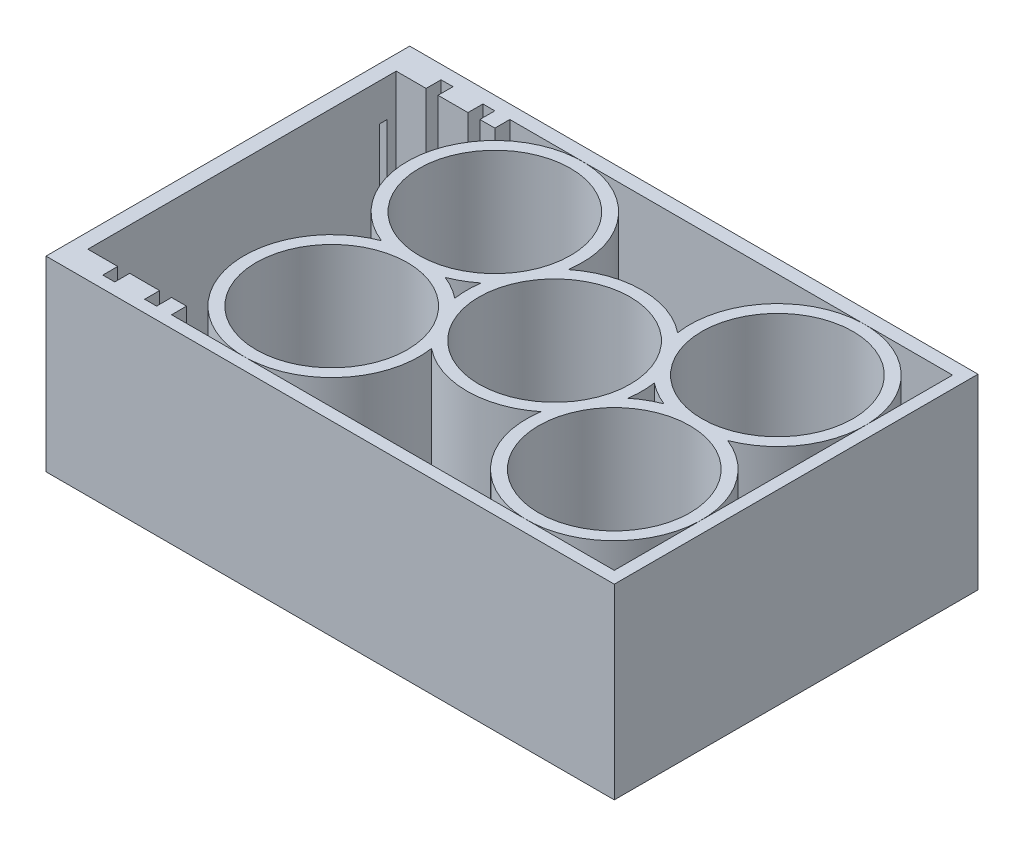
SolidWorks part; units mm, degrees
ref_plane "Front Plane" through (0, 0, 0) normal (0, 0, 1) x (1, 0, 0)
ref_plane "Top Plane" through (0, 0, 0) normal (0, 1, 0) x (1, 0, 0)
ref_plane "Right Plane" through (0, 0, 0) normal (1, 0, 0) x (0, 0, -1)
sketch "Sketch1" plane through (0, 0, 0) normal (0, 1, 0) x (1, 0, 0)
  line L0 (22.3334, 17.5114) -> (22.3334, 7.3964)
  line L1 (22.3334, 29.2264) -> (3.428, 18.3114)
  line L2 (3.428, 18.3114) -> (-15.4773, 29.2264)
  line L3 (-15.4773, 17.5114) -> (-15.4773, 7.3964)
  line L4 (34.0484, 40.9414) -> (34.0484, -4.3186)
  line L5 (-27.1923, 7.3964) -> (-27.1923, 18.3114)
  line L6 (-27.1923, 18.3114) -> (34.0484, 18.3114)
  line L7 (-27.1923, 40.9414) -> (-28.7923, 40.9414)
  line L9 (-27.1923, 40.9414) -> (-27.1923, -4.3186)
  line L11 (-28.7923, 40.9414) -> (-28.7923, -4.3186)
  line L12 (-28.7923, -4.3186) -> (-27.1923, -4.3186)
  line L13 (-27.1923, 38.9414) -> (-25.1923, 38.9414)
  line L14 (-32.7923, 40.9414) -> (-32.7923, -4.3186)
  line L15 (-25.1923, 38.9414) -> (-25.1923, 40.9414)
  line L16 (-34.3923, 40.9414) -> (-32.7923, 40.9414)
  line L18 (-34.3923, 40.9414) -> (-34.3923, -4.3186)
  line L22 (-34.3923, -4.3186) -> (-32.7923, -4.3186)
  line L23 (-25.1923, 40.9414) -> (34.0484, 40.9414)
  line L24 (-38.3923, 38.9414) -> (-38.3923, -2.3186)
  line L25 (-27.1923, -2.3186) -> (-25.1923, -2.3186)
  line L29 (-34.3923, 40.9414) -> (-34.3923, 38.9414)
  line L32 (-34.3923, 38.9414) -> (-38.3923, 38.9414)
  line L36 (-32.7923, 38.9414) -> (-28.7923, 38.9414)
  line L40 (-34.3923, -4.3186) -> (-34.3923, -2.3186)
  line L41 (-34.3923, -2.3186) -> (-38.3923, -2.3186)
  line L42 (-32.7923, -2.3186) -> (-28.7923, -2.3186)
  line L43 (-25.1923, -2.3186) -> (-25.1923, -4.3186)
  line L44 (-25.1923, -4.3186) -> (34.0484, -4.3186)
  line L45 (-34.3923, 38.9414) -> (-38.3923, 38.9414)
  line L46 (-32.7923, 40.9414) -> (-34.3923, 40.9414)
  line L47 (-32.7923, 40.9414) -> (-32.7923, -4.3186)
  line L48 (-32.7923, -4.3186) -> (-34.3923, -4.3186)
  line L49 (-34.3923, 40.9414) -> (-34.3923, -4.3186)
  line L50 (-38.3923, -2.3186) -> (-34.9331, -2.3186)
  line L51 (-25.1923, 38.9414) -> (-27.1923, 38.9414)
  line L52 (-28.7923, 38.9414) -> (-32.7923, 38.9414)
  line L53 (-34.3923, 38.9414) -> (-38.3923, 38.9414)
  line L54 (-38.3923, -2.3186) -> (-34.3923, -2.3186)
  line L55 (-32.7923, -2.3186) -> (-28.7923, -2.3186)
  line L56 (-27.1923, -2.3186) -> (-25.1923, -2.3186)
  line L57 (-25.1923, -2.3186) -> (-25.1923, -4.3186)
  line L58 (34.0484, -4.3186) -> (-25.1923, -4.3186)
  line L59 (34.0484, 40.9414) -> (34.0484, -4.3186)
  line L61 (35.6484, -5.9186) -> (-40.3923, -5.9186)
  line L62 (35.6484, -5.9186) -> (35.6484, 42.7484)
  line L63 (35.6484, 42.7484) -> (-40.3923, 42.7484)
  line L64 (-40.3923, -5.9186) -> (-40.3923, 42.7484)
  line L65 (34.0484, -4.3186) -> (-38.3923, -4.3186)
  line L66 (34.0484, -4.3186) -> (34.0484, 40.9414)
  line L67 (34.0484, 40.9414) -> (-38.3923, 40.9414)
  line L68 (-38.3923, -4.3186) -> (-38.3923, 40.9414)
  line L69 (-40.3923, 42.7484) -> (35.6484, 42.7484)
  line L70 (-40.3923, 42.7484) -> (-40.3923, -5.9186)
  line L71 (-40.3923, -5.9186) -> (35.6484, -5.9186)
  line L72 (35.6484, 42.7484) -> (35.6484, -5.9186)
  circle A0 centre (22.3334, 29.2264) radius 10.115
  circle A1 centre (22.3334, 29.2264) radius 11.715
  circle A2 centre (22.3334, 7.3964) radius 10.115
  circle A3 centre (22.3334, 7.3964) radius 11.715
  circle A4 centre (3.428, 18.3114) radius 10.115
  circle A5 centre (3.428, 18.3114) radius 11.715
  circle A6 centre (-15.4773, 29.2264) radius 11.715
  circle A7 centre (-15.4773, 29.2264) radius 10.115
  circle A8 centre (-15.4773, 7.3964) radius 10.115
  circle A9 centre (-15.4773, 7.3964) radius 11.715
extrude "Boss-Extrude4" add sketch "Sketch1" along normal blind 25 contours L64 L61 L62 L63 L65 L68 L24 L67 L16 L7 L23 L4 L66 L44 L12 L22 | L68 L65 L18 L41 | L68 L32 L18 L67 | A9 A7 A5 A6 | A9 A5 A8 A6 | A6 L6 | L6 A9 | A9 A6 A5 A7 | A5 A9 A6 A8 | A5 A6 L2 | L2 A6 A5 | A6 A4 A1 A5 | A6 A5 L6 A4 | A9 A4 L6 A5 | A5 A9 | A9 A5 A3 A4 | A5 A0 A3 A1 | L1 A5 A1 | A1 A5 L1 | A5 A1 A3 A0 | L6 A5 A1 A4 | A3 A5 L6 A4 | A3 A5 | L6 A3 | A1 L6 | A5 A2 A1 A3 | A5 A3 A1 A2 | L15 L67 L9 L13 | L11 L67 L14 L36 | L65 L11 L42 L14 | L65 L43 L25 L9 | A6 | A4 region at (13.6822, 0, -22.3806) region at (12.5636, 0, -26.1549) region at (17.0188, 0, -20.0213) region at (12.0791, 0, -25.1572) region at (3.428, 0, -28.6138) region at (14.0571, 0, -19.8388) region at (22.3334, 0, -18.6324) region at (14.0571, 0, -16.784) region at (-6.8262, 0, -22.3806) region at (-7.2011, 0, -19.8388) region at (-5.2231, 0, -25.1572) region at (22.3334, 0, -17.9905) region at (31.7362, 0, -13.823) region at (17.0188, 0, -16.6015) region at (-5.7076, 0, -26.1549) region at (-7.2011, 0, -16.784) region at (12.8807, 0, -12.8539) region at (11.1034, 0, -11.3404) region at (-10.1628, 0, -20.0213) region at (-6.0247, 0, -12.8539) region at (-15.4773, 0, -18.6324) region at (-15.4773, 0, -17.9905) region at (-10.1628, 0, -16.6015) region at (-26.1923, 0, -39.9414) region at (-4.1209, 0, -8.2606) region at (-26.1923, 0, 3.3186) region at (-30.7923, 0, -39.9414) region at (-30.7923, 0, 3.3186) region at (-36.3923, 0, -39.9414) region at (-36.3923, 0, 3.3186) region at (-2.372, 0, 5.0158)
extrude "Cut-Extrude1" cut sketch "Sketch1<9>" along normal blind 36 contours L6 A4 L1 | L1 A4 L2 | L2 A4 L6 | A4 L6 | A7 region at (9.8674, 0, -20.0368) region at (3.428, 0, -23.8881) region at (-3.0114, 0, -20.0368) region at (3.428, 0, -14.0185) region at (-10.5629, 0, -20.7143)
sketch "Sketch1<9>" plane through (0, 0, 0) normal (0, 1, 0) x (1, 0, 0) same geometry as "Sketch1"
sketch "Sketch3" plane through (0, 0, 0) normal (0, -1, 0) x (1, 0, 0)
  line L1 (-40.3923, 5.9186) -> (35.6484, 5.9186)
  line L2 (-40.3923, 5.9186) -> (-40.3923, -42.7484)
  line L3 (-40.3923, -42.7484) -> (35.6484, -42.7484)
  line L4 (35.6484, 5.9186) -> (35.6484, -42.7484)
sketch "Sketch4" plane through (-40.3923, 0, 0) normal (-1, 0, 0) x (0, 0, 1)
  line L14 (-34.6849, 20) -> (-2.018, 20)
  line L19 (-34.6849, 20) -> (-34.6849, 5)
  line L21 (-34.6849, 5) -> (-2.018, 5)
  line L22 (-2.018, 20) -> (-2.018, 5)
  line L23 (-0.018, 5) -> (0.982, 5)
  line L24 (-0.018, 5) -> (-0.018, 20)
  line L25 (-0.018, 20) -> (0.982, 20)
  line L26 (0.982, 5) -> (0.982, 20)
  line L32 (-36.6849, 20) -> (-37.6849, 20)
  line L33 (-36.6849, 20) -> (-36.6849, 5)
  line L34 (-36.6849, 5) -> (-37.6849, 5)
  line L35 (-37.6849, 20) -> (-37.6849, 5)
extrude "Cut-Extrude3" cut sketch "Sketch4" against normal blind 3 contours L24 L23 L26 L25 | L33 L32 L35 L34
sketch "Sketch5" plane through (-40.3923, 0, 0) normal (-1, 0, 0) x (0, 0, 1)
  line L1 (-37.6849, 20) -> (0.982, 20)
  line L2 (-37.6849, 20) -> (-37.6849, 5)
  line L3 (-37.6849, 5) -> (0.982, 5)
  line L4 (0.982, 20) -> (0.982, 5)
extrude "Cut-Extrude4" cut sketch "Sketch5" against normal blind 0.5
